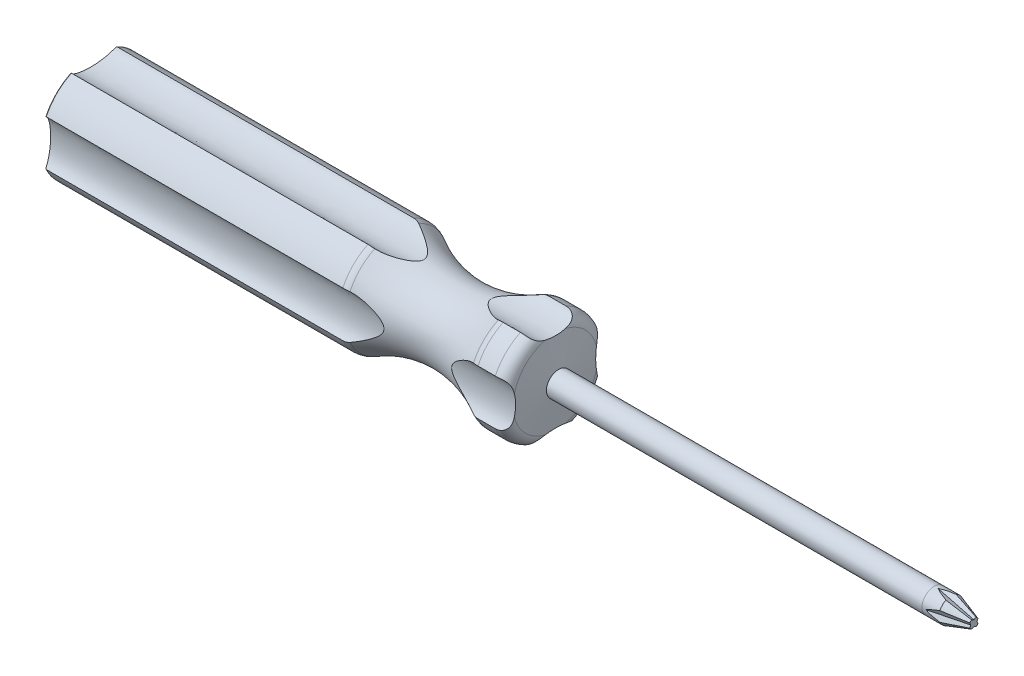
SolidWorks part; units mm, degrees
ref_plane "Front Plane" through (0, 0, 0) normal (0, 0, 1) x (1, 0, 0)
ref_plane "Top Plane" through (0, 0, 0) normal (0, 1, 0) x (1, 0, 0)
ref_plane "Right Plane" through (0, 0, 0) normal (1, 0, 0) x (0, 0, -1)
sketch "Sketch1" plane through (0, 0, 0) normal (0, 0, 1) x (1, 0, 0)
  line L0 (0, 0) -> (113.716, 0)
  line L1 (0, 4) -> (113.716, 4)
  line L2 (113.716, 4) -> (121.1868, 1.5209)
  line L3 (121.1868, 1.5209) -> (121.1868, 0)
  line L4 (121.1868, 0) -> (113.716, 0)
  line L6 (0, 4) -> (-66.9286, 4)
  line L8 (0, 0) -> (-66.9286, 0)
  line L9 (-66.9286, 4) -> (-66.9286, 0)
  dimension "D1" = 4
revolve "Revolve1" add sketch "Sketch1" angle 360 about L8
sketch "Sketch5" plane through (-66.9286, 0, 0) normal (-1, 0, 0) x (0, 0, 1)
  circle A0 centre (-3.5737, -1.7969) radius 0.5392
  circle A1 centre (0, 0) radius 4 construction
  circle A2 centre (-3.343, 2.1964) radius 0.5392
  circle A3 centre (0.2306, 3.9933) radius 0.5392
  circle A4 centre (3.5737, 1.7969) radius 0.5392
  circle A5 centre (3.343, -2.1964) radius 0.5392
  circle A6 centre (-0.2306, -3.9933) radius 0.5392
  point P16 (0, 0)
  dimension "D1" = 6
extrude "Cut-Extrude3" cut sketch "Sketch5" against normal blind 24
sketch "Sketch2" plane through (0, 0, 0) normal (0, 0, 1) x (1, 0, 0)
  line L0 (121.4761, 0.9266) -> (107.6653, 4.4647)
  line L1 (107.6653, 4.4647) -> (121.4761, 4.4647)
  line L2 (121.4761, 4.4647) -> (121.4761, 0.9266)
extrude "Cut-Extrude1" cut sketch "Sketch2" against normal blind 3 draft 23 and the other way blind 3 draft 23
pattern_circular "CirPattern1" count 4 over 360 about axis through (121.1868, 0, 0) along (1, 0, 0) of "Cut-Extrude1"
sketch "Sketch3" plane through (0, 0, 0) normal (0, 0, 1) x (1, 0, 0)
  line L0 (-14.7049, 4) -> (-66.9286, 4)
  line L1 (109.4791, 4) -> (-42.9286, 4) construction
  line L2 (-66.9286, 4) -> (-66.9286, 0)
  line L3 (-66.9286, 4) -> (-66.9286, -4) construction
  line L4 (-66.9286, 0) -> (-168.5108, 0)
  line L6 (-166.6614, 17.4031) -> (-68.59, 17.4031)
  line L7 (-16.1421, 17.4031) -> (-14.7049, 4)
  line L10 (-26.4143, 17.4031) -> (-16.1421, 17.4031)
  ellipse E0 centre (-166.6614, 0) end of major axis (-166.6614, 17.4031) minor radius 1.8494 (-166.6614, 17.4031) -> (-168.5108, 0) ccw
  spline S0 degree 3 poles (-68.59, 17.4031) (-62.8793, 14.1005) (-49.0363, 9.4869) (-34.8234, 12.7895) (-26.4143, 17.4031) knots 0.086154 0.086154 0.086154 0.086154 0.431459 0.913846 0.913846 0.913846 0.913846
revolve "Revolve2" add sketch "Sketch3" angle 360 about L4
fillet "Fillet1" radius 4 3 edges at (-16.1421, 0, -17.4031) (-26.4143, 0, -17.4031) (-68.59, 0, -17.4031)
sketch "Sketch4" plane through (0, 0, 0) normal (1, 0, 0) x (0, 0, -1)
  ellipse E0 centre (0, 16.4526) end of major axis (7.658, 16.4526) minor radius 3.3504
extrude "Cut-Extrude2" cut sketch "Sketch4" against normal blind 175
pattern_circular "CirPattern2" count 4 over 360 about axis through (-14.7049, 0, 0) along (1, 0, 0) of "Cut-Extrude2"
sketch "Sketch6" plane through (0, 0, 0) normal (0, 0, 1) x (1, 0, 0)
  line L1 (124.1178, 8.0824) -> (108.2163, 8.0824)
  line L2 (124.1178, 8.0824) -> (124.1178, -7.53)
  line L3 (124.1178, -7.53) -> (108.2163, -7.53)
  line L4 (108.2163, 8.0824) -> (108.2163, -7.53)
split line "Split Line1"
